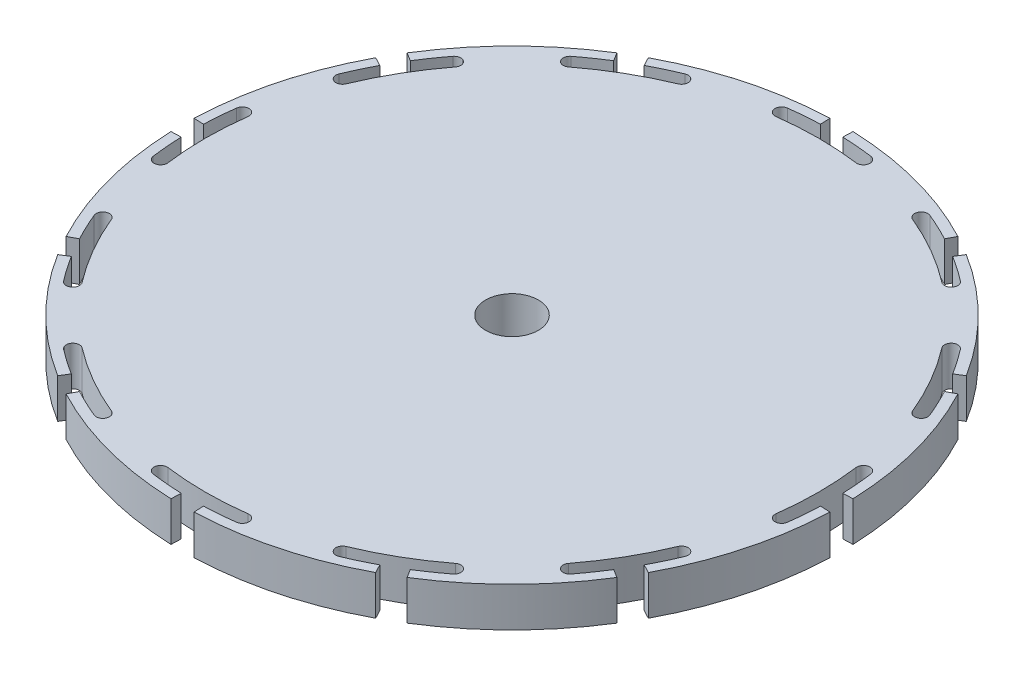
SolidWorks part; units mm, degrees
ref_plane "Front Plane" through (0, 0, 0) normal (0, 0, 1) x (1, 0, 0)
ref_plane "Top Plane" through (0, 0, 0) normal (0, 1, 0) x (1, 0, 0)
ref_plane "Right Plane" through (0, 0, 0) normal (1, 0, 0) x (0, 0, -1)
sketch "Sketch1" plane through (0, 0, 0) normal (0, 1, 0) x (1, 0, 0)
  circle A0 centre (0, 0) radius 50
  dimension "D1" = 100
sketch "Sketch2" plane through (0, 0, 0) normal (0, 1, 0) x (1, 0, 0)
  line L0 (0, 0) -> (0, 50) construction
  line L1 (-1.745, 49.9695) -> (0, 0) construction
  line L2 (0, 0) -> (-6.5263, 49.5722) construction
  line L3 (-1.745, 49.9695) -> (-1.6926, 48.4705)
  line L4 (0, 0) -> (6.5263, 49.5722) construction
  line L5 (1.745, 49.9695) -> (0, 0) construction
  line L6 (1.745, 49.9695) -> (1.6926, 48.4705)
  arc A0 (6.0695, 46.1022) -> (-6.0695, 46.1022) centre (0, 0) ccw
  circle A1 centre (0, 0) radius 50 construction
  arc A2 (-1.745, 49.9695) -> (1.745, 49.9695) centre (0, 0) cw
  arc A3 (-1.6926, 48.4705) -> (-6.3305, 48.0851) centre (0, 0) ccw
  arc A4 (-6.0695, 46.1022) -> (-6.3305, 48.0851) centre (-6.2, 47.0936) cw
  arc A5 (6.0695, 46.1022) -> (6.3305, 48.0851) centre (6.2, 47.0936) ccw
  arc A6 (1.6926, 48.4705) -> (6.3305, 48.0851) centre (0, 0) cw
  point P130 (0, 0)
  dimension "D1" = 15
  dimension "D2" = 2
  dimension "D4" = 1.5
  dimension "D3" = 4
sketch "Sketch3" plane through (0, 0, 0) normal (0, 1, 0) x (1, 0, 0)
  circle A0 centre (0, 0) radius 4
  dimension "D1" = 8
extrude "Wheel Blank" add sketch "Sketch1" along normal blind 6
extrude "T-Slot" cut sketch "Sketch2" along normal through all
pattern_circular "CirPattern" count 12 over 360 about axis through (0, 6, 0) along (0, -1, 0) of "T-Slot"
extrude "Center Hole" cut sketch "Sketch3" along normal blind 6
